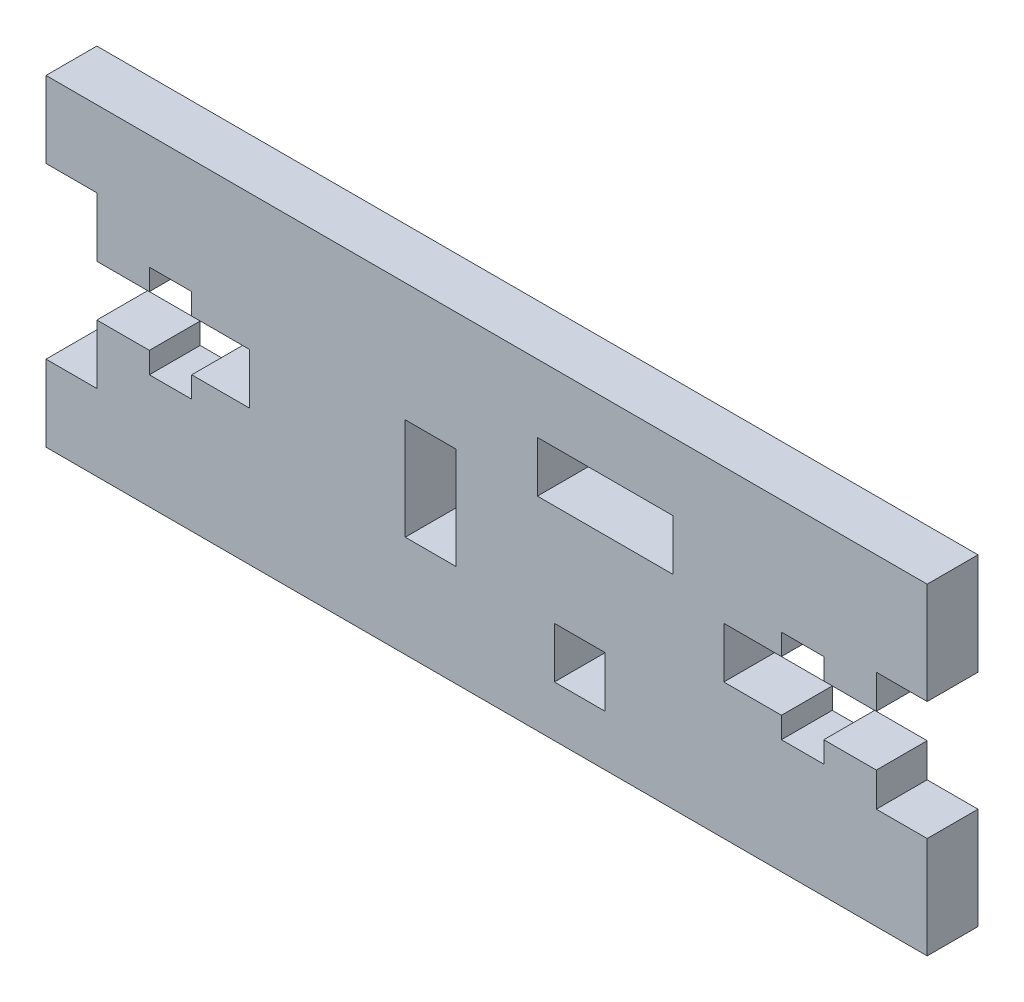
SolidWorks part; units mm, degrees
note: '?' marks a value the reader was unsure of.
material "Acrílico (médio-alto impacto)"
ref_plane "Plano frontal" through (0, 0, 0) normal (0, 0, 1) x (1, 0, 0)
ref_plane "Plano superior" through (0, 0, 0) normal (0, 1, 0) x (1, 0, 0)
ref_plane "Plano direito" through (0, 0, 0) normal (1, 0, 0) x (0, 0, -1)
sketch "Esboço1" plane through (0, 0, 0) normal (0, 0, 1) x (1, 0, 0)
  line L1 (-23, -9.5) -> (23, -9.5)
  line L2 (-23, -9.5) -> (-23, 9.5)
  line L3 (-23, 9.5) -> (23, 9.5)
  line L4 (23, -9.5) -> (23, 9.5)
  line L5 (0, 9.5) -> (0, -9.5) construction
  line L6 (-23, 0) -> (23, 0) construction
  point P0 (0, 0)
  dimension "D1" = 19
  dimension "D2" = 46
sketch "Esboço3" plane through (0, 0, 0) normal (0, 0, 1) x (1, 0, 0)
  line L1 (-23, -9.5) -> (-26, -9.5)
  line L2 (-23, -9.5) -> (-23, -5)
  line L3 (-23, -5) -> (-26, -5)
  line L4 (-26, -9.5) -> (-26, -5)
  dimension "D1" = 4.5
  dimension "D2" = 3
sketch "Esboço4" plane through (0, 0, 0) normal (0, 0, 1) x (1, 0, 0)
  line L0 (-23, 0) -> (23, 0) construction
  line L2 (23, 9.5) -> (26, 9.5)
  line L3 (23, 9.5) -> (23, 3.5)
  line L4 (23, 3.5) -> (26, 3.5)
  line L5 (26, 9.5) -> (26, 3.5)
  line L6 (23, -9.5) -> (26, -9.5)
  line L7 (23, -9.5) -> (23, -3.5)
  line L8 (23, -3.5) -> (26, -3.5)
  line L9 (26, -9.5) -> (26, -3.5)
  dimension "D1" = 6
  dimension "D2" = 3
sketch "Dente" plane through (0, 0, 0) normal (0, 0, 1) x (1, 0, 0)
  line L0 (-23, -9.5) -> (23, -9.5) construction
  line L1 (4, -6.5) -> (7, -6.5)
  line L2 (4, -6.5) -> (4, -3.5)
  line L3 (4, -3.5) -> (7, -3.5)
  line L4 (7, -6.5) -> (7, -3.5)
  line L6 (23, -9.5) -> (23, 9.5) construction
  dimension "D1" = 3
  dimension "D2" = 3
  dimension "D3" = 16
sketch "Esboço6" plane through (0, 0, 0) normal (0, 0, 1) x (1, 0, 0)
  line L1 (-4.8, -3.5) -> (-1.8, -3.5)
  line L2 (-4.8, -3.5) -> (-4.8, 2.5)
  line L3 (-4.8, 2.5) -> (-1.8, 2.5)
  line L4 (-1.8, -3.5) -> (-1.8, 2.5)
  line L6 (-23, -9.5) -> (23, -9.5) construction
  line L11 (-23, -9.5) -> (-23, 9.5) construction
  dimension "D1" = 18.2
  dimension "D2" = 3
  dimension "D3" = 6
  dimension "D4" = 6
sketch "Esboço23" plane through (0, 0, 0) normal (0, 0, 1) x (1, 0, 0)
  line L0 (23, -9.5) -> (23, 9.5) construction
  line L1 (3, 5.5) -> (11, 5.5)
  line L2 (3, 5.5) -> (3, 2.5)
  line L3 (3, 2.5) -> (11, 2.5)
  line L4 (11, 5.5) -> (11, 2.5)
  line L5 (7, 2.5) -> (7, 5.5) construction
  line L6 (3, 4) -> (11, 4) construction
  line L7 (-23, 9.5) -> (23, 9.5) construction
  point P0 (7, 4)
  dimension "D1" = 8
  dimension "D2" = 3
  dimension "D3" = 12
  dimension "D4" = 4
extrude "Ressalto-extrusão1" add sketch "Esboço1" along normal mid plane 3
extrude "Corte-extrusão3" cut sketch "Esboço6" against normal through all both and the other way through all
extrude "Corte-extrusão2" cut sketch "Dente" against normal through all both and the other way through all
extrude "Ressalto-extrusão3" add sketch "Esboço4" along normal through all and the other way through all
sketch "Esboço21" plane through (2.823, -2.2847, 1.5) normal (0, 0, 1) x (1, 0, 0)
  line L0 (-25.823, 2.2847) -> (-16.823, 2.2847) construction
  line L2 (-25.823, 11.7847) -> (-25.823, -7.2153) construction
  line L3 (-25.823, 0.7847) -> (-16.823, 0.7847)
  line L4 (-25.823, 0.7847) -> (-25.823, 3.7847)
  line L5 (-25.823, 3.7847) -> (-16.823, 3.7847)
  line L6 (-16.823, 0.7847) -> (-16.823, 3.7847)
  line L7 (-21.323, 3.7847) -> (-21.323, 0.7847) construction
  line L8 (-25.823, 2.2847) -> (-16.823, 2.2847) construction
  line L9 (-22.723, 5.0347) -> (-20.223, 5.0347)
  line L10 (-22.723, 5.0347) -> (-22.723, -0.4653)
  line L11 (-22.723, -0.4653) -> (-20.223, -0.4653)
  line L12 (-20.223, 5.0347) -> (-20.223, -0.4653)
  line L13 (-21.473, -0.4653) -> (-21.473, 5.0347) construction
  line L14 (-22.723, 2.2847) -> (-20.223, 2.2847) construction
  line L15 (-25.823, 11.7847) -> (-25.823, -7.2153) construction
  point P5 (-21.323, 2.2847)
  point P9 (-21.473, 2.2847)
  dimension "D1" = 3.1
  dimension "D2" = 5.5
  dimension "D3" = 3
  dimension "D4" = 2.5
  dimension "D6" = 9
  dimension "Posicionar" = 9.5
extrude "Corte-extrusão11" cut sketch "Esboço21" against normal blind 3 contours L5 L6 L3 L4 | L10 L11 L12 L9
other "Porca e parafuso<1>"
mirror "Espelhar3" about plane through (0, 0, 0) normal (1, 0, 0) of "Corte-extrusão11"
ref_axis "Eixo1" through (-23, 0, 0) along (1, 0, 0)?
extrude "Ressalto-extrusão2" add sketch "Esboço3" along normal through all and the other way through all contours L4 L3 L2 L1
mirror "Espelhar2" about plane through (0, 0, 0) normal (0, 1, 0) of "Corte-extrusão11", "Ressalto-extrusão2"
extrude "Corte-extrusão12" cut sketch "Esboço23" against normal through all both and the other way through all contours L3 L4 L1 L2
ref_plane "Plano1" through (0, 4, 0) normal (0, 1, 0) x (1, 0, 0)
sketch "Esboço24" plane through (0, 4, 0) normal (0, 1, 0) x (1, 0, 0)
  line L0 (7, 1.5) -> (7, -1.5)
  line L1 (3, 1.5) -> (11, 1.5) construction
  line L2 (3, -1.5) -> (11, -1.5) construction
other "PontoR1"
other "PontoR2"
ref_axis "Eixo2" through (7, 4, -1.5) along (0, 0, 1)?
